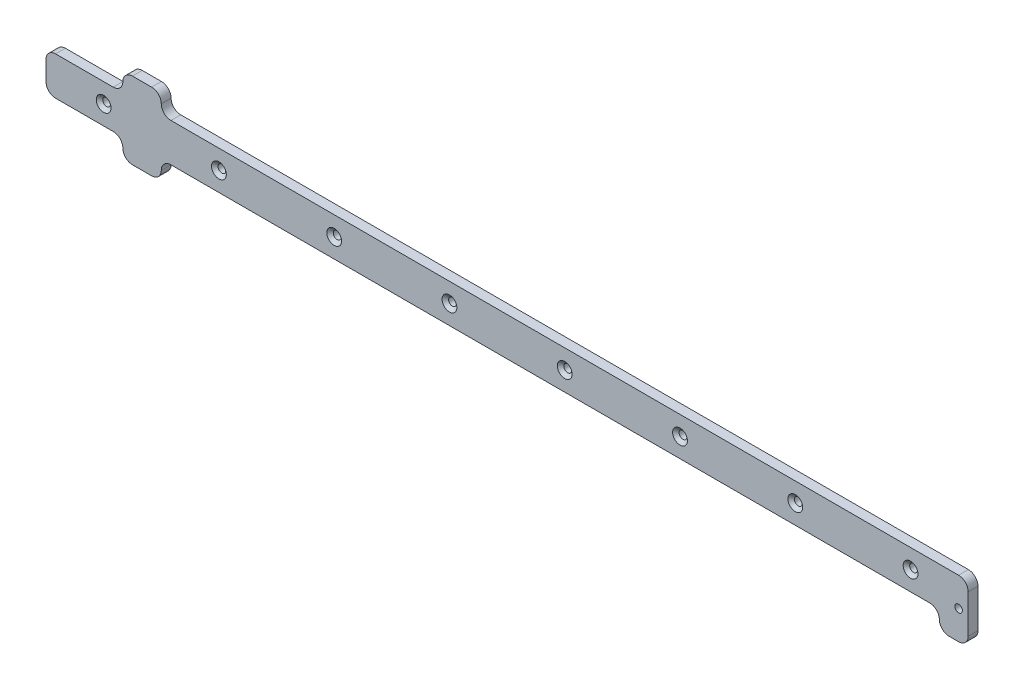
SolidWorks part; units mm, degrees
material "PC High Viscosity"
ref_plane "Front Plane" through (0, 0, 0) normal (0, 0, 1) x (1, 0, 0)
ref_plane "Top Plane" through (0, 0, 0) normal (0, 1, 0) x (1, 0, 0)
ref_plane "Right Plane" through (0, 0, 0) normal (1, 0, 0) x (0, 0, -1)
sketch "Sketch1" plane through (0, 0, 0) normal (0, 0, 1) x (1, 0, 0)
  line L0 (50.8, 0) -> (50.8, -12.7)
  line L1 (0, 0) -> (590.55, 0)
  line L2 (0, 0) -> (0, 25.4)
  line L3 (0, 25.4) -> (609.6, 25.4)
  line L4 (609.6, 0) -> (609.6, 25.4)
  line L5 (50.8, 38.1) -> (76.2, 38.1)
  line L6 (76.2, 38.1) -> (76.2, 25.4)
  line L7 (50.8, 38.1) -> (50.8, 25.4)
  line L8 (76.2, 0) -> (76.2, -12.7)
  line L9 (76.2, -12.7) -> (50.8, -12.7)
  line L10 (590.55, 0) -> (590.55, -12.7)
  line L11 (609.6, 10.0162) -> (603.25, 13.6823) construction
  line L12 (603.25, 13.6823) -> (596.9, 10.0162) construction
  line L13 (596.9, 10.0162) -> (596.9, 2.6838) construction
  line L14 (596.9, 2.6838) -> (603.25, -0.9823) construction
  line L15 (603.25, -0.9823) -> (609.6, 2.6838) construction
  line L16 (609.6, 2.6838) -> (609.6, 10.0162) construction
  line L17 (609.6, 0) -> (609.6, -12.7)
  line L18 (609.6, -12.7) -> (590.55, -12.7)
  circle A0 centre (603.25, 6.35) radius 2.4892
  circle A1 centre (603.25, 6.35) radius 6.35 construction
  dimension "D5" = 4.9784
  dimension "D6" = 12.7
  dimension "D7" = 12.7
  dimension "D1" = 609.6
  dimension "D2" = 25.4
  dimension "D3" = 25.4
  dimension "D4" = 50.8
  dimension "D8" = 19.05
  dimension "D9" = 12.7
extrude "Boss-Extrude1" add sketch "Sketch1" along normal blind 6.477 contours L6 L5 L3 | L1 L4 L3 L2 A0 | L9 L8 L1 region at (63.5, -6.35, 0) region at (308.9784, 12.4144, 0) region at (63.5, 31.75, 0)
fillet "Fillet2" radius 6.35 14 edges at (76.2, 38.1, 3.2385) (76.2, 25.4, 3.2385) (609.6, 25.4, 3.2385) (76.2, 0, 3.2385) (76.2, -12.7, 3.2385) (50.8, -12.7, 3.2385) (50.8, 0, 3.2385) (0, 0, 3.2385) (50.8, 38.1, 3.2385) (50.8, 25.4, 3.2385) (0, 25.4, 3.2385) (590.55, 0, 3.2385) (590.55, -12.7, 3.2385) (609.6, -12.7, 3.2385)
sketch "Sketch2" plane through (0, 0, 6.477) normal (0, 0, 1) x (1, 0, 0)
  line L0 (82.55, 25.4) -> (603.25, 25.4) construction
  line L1 (609.6, 19.05) -> (609.6, -6.35) construction
  circle A0 centre (571.5, 12.7) radius 2.0193
  dimension "D1" = 4.0386
  dimension "D2" = 12.7
  dimension "D3" = 38.1
hole_wizard "CSK for #10 Flat Head Machine Screw (100)1" positions "Sketch4" profile "Sketch5" countersink size "#10" standard "ANSI Inch" end condition through all
sketch "Sketch4" plane through (0, 0, 6.477) normal (0, 0, 1) x (1, 0, 0)
  line L0 (609.6, 12.7) -> (0, 12.7) construction
  line L1 (609.6, 19.05) -> (609.6, -6.35) construction
  line L2 (0, 6.35) -> (0, 19.05) construction
  line L3 (82.55, 25.4) -> (603.25, 25.4) construction
  point P11 (571.5, 12.7)
  dimension "D1" = 12.7
  dimension "D2" = 38.1
sketch "Sketch5" plane through (571.5, 12.7, 6.477) normal (1, 0, 0) x (0, -1, 0)
  line L0 (0, 0) -> (0, 6.477)
  line L1 (0, 6.477) -> (2.5527, 6.477)
  line L2 (2.5527, 6.477) -> (2.5527, 1.9608)
  line L3 (2.5527, 1.9608) -> (4.8895, 0)
  line L5 (4.8895, 0) -> (0, 0)
  line L6 (-2.5527, 1.9608) -> (-4.8895, 0) construction
  line L11 (0, -6.35) -> (0, 107.95) construction
  dimension "Thru Hole Dia." = 5.1054
  dimension "Thru Hole Depth" = 6.477
  dimension "Near C'Sink Dia." = 9.779
  dimension "Near C'Sink Angle" = 100
pattern_linear "LPattern1" count 8 spacing 76.2 along (-1, 0, 0) of "CSK for #10 Flat Head Machine Screw (100)1"
